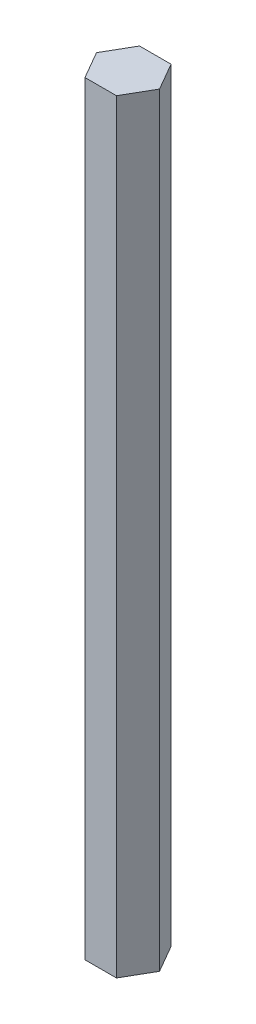
SolidWorks part; units mm, degrees
material "6061 Alloy"
ref_plane "Front Plane" through (0, 0, 0) normal (0, 0, 1) x (1, 0, 0)
ref_plane "Top Plane" through (0, 0, 0) normal (0, 1, 0) x (1, 0, 0)
ref_plane "Right Plane" through (0, 0, 0) normal (1, 0, 0) x (0, 0, -1)
sketch "Sketch1" plane through (0, 0, 0) normal (0, 1, 0) x (1, 0, 0)
  line L1 (7.3323, 0) -> (3.6662, 6.35)
  line L2 (3.6662, 6.35) -> (-3.6662, 6.35)
  line L3 (-3.6662, 6.35) -> (-7.3323, 0)
  line L4 (-7.3323, 0) -> (-3.6662, -6.35)
  line L5 (-3.6662, -6.35) -> (3.6662, -6.35)
  line L6 (3.6662, -6.35) -> (7.3323, 0)
  circle A0 centre (0, 0) radius 6.35 construction
extrude "Boss-Extrude1" add sketch "Sketch1" along normal blind 177.8 contours L2 L3 L4 L5 L6 L1
ref_axis "Axis1" through (0, -8.255, 0) along (0, 1, 0)
